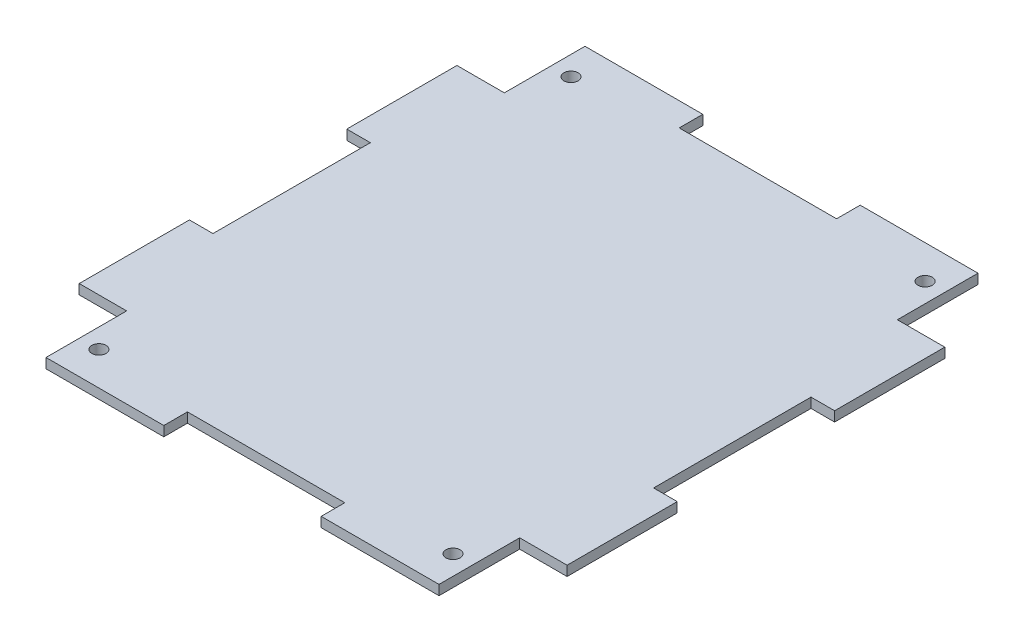
SolidWorks part; units mm, degrees
ref_plane "Front Plane" through (0, 0, 0) normal (0, 0, 1) x (1, 0, 0)
ref_plane "Top Plane" through (0, 0, 0) normal (0, 1, 0) x (1, 0, 0)
ref_plane "Right Plane" through (0, 0, 0) normal (1, 0, 0) x (0, 0, -1)
sketch "Sketch1" plane through (0, 0, 0) normal (0, 1, 0) x (1, 0, 0)
  line L0 (-25.4, 86.995) -> (-63.4314, 86.995)
  line L1 (-88.9, -101.6) -> (88.9, -101.6) construction
  line L2 (101.6, -88.9) -> (101.6, 88.9) construction
  line L3 (88.9, 101.6) -> (-88.9, 101.6) construction
  line L4 (-78.74, -60.96) -> (-63.4314, -60.96)
  line L5 (-63.4314, -60.96) -> (-63.4314, -86.995)
  line L6 (-63.4314, -86.995) -> (-25.4, -86.995)
  line L7 (63.4314, -86.995) -> (63.4314, -60.96)
  line L8 (63.4314, -60.96) -> (78.74, -60.96)
  line L9 (78.74, -60.96) -> (78.74, -25.4)
  line L10 (78.74, 60.96) -> (63.4314, 60.96)
  line L11 (63.4314, 60.96) -> (63.4314, 86.995)
  line L12 (63.4314, 86.995) -> (25.4, 86.995)
  line L13 (-63.4314, 86.995) -> (-63.4314, 60.96)
  line L14 (-63.4314, 60.96) -> (-78.74, 60.96)
  line L15 (-78.74, 60.96) -> (-78.74, 25.4)
  line L16 (-78.74, -25.4) -> (-78.74, -60.96)
  line L17 (-78.74, -25.4) -> (-71.12, -25.4)
  line L19 (-78.74, 25.4) -> (-71.12, 25.4)
  line L20 (-71.12, -25.4) -> (-71.12, 25.4)
  line L22 (-25.4, 86.995) -> (-25.4, 79.375)
  line L23 (-25.4, 79.375) -> (25.4, 79.375)
  line L24 (25.4, 86.995) -> (25.4, 79.375)
  line L25 (78.74, 25.4) -> (71.12, 25.4)
  line L27 (78.74, -25.4) -> (71.12, -25.4)
  line L28 (71.12, 25.4) -> (71.12, -25.4)
  line L30 (25.4, -86.995) -> (25.4, -79.375)
  line L31 (25.4, -79.375) -> (-25.4, -79.375)
  line L32 (-25.4, -86.995) -> (-25.4, -79.375)
  line L33 (78.74, 25.4) -> (78.74, 60.96)
  line L34 (25.4, -86.995) -> (63.4314, -86.995)
  line L35 (-101.6, 88.9) -> (-101.6, -88.9) construction
  arc A0 (88.9, -101.6) -> (101.6, -88.9) centre (88.9, -88.9) ccw construction
  arc A1 (-101.6, -88.9) -> (-88.9, -101.6) centre (-88.9, -88.9) ccw construction
  arc A2 (101.6, 88.9) -> (88.9, 101.6) centre (88.9, 88.9) ccw construction
  arc A3 (-101.6, 88.9) -> (-88.9, 101.6) centre (-88.9, 88.9) cw construction
  circle A4 centre (-57.15, 76.2) radius 2.286
  circle A5 centre (57.15, 76.2) radius 2.286
  circle A6 centre (57.15, -76.2) radius 2.286
  circle A7 centre (-57.15, -76.2) radius 2.286
  point P3 (0, 101.6)
  point P5 (101.6, 0)
  point P13 (101.6, 101.6)
  point P16 (-101.6, 101.6)
  point P38 (-71.12, 0)
  point P55 (0, -79.375)
  point P56 (0, 79.375)
  point P57 (71.12, 0)
  dimension "D2" = 12.7
  dimension "D11" = 4.572
  dimension "D8" = 44.45
  dimension "D1" = 203.2
  dimension "D3" = 203.2
  dimension "D4" = 22.86
  dimension "D5" = 15.3086
  dimension "D6" = 35.56
  dimension "D7" = 173.99
  dimension "D12" = 50.8
  dimension "D13" = 25.4
  dimension "D14" = 44.45
  dimension "D15" = 25.4
  dimension "D18" = 7.62
extrude "Boss-Extrude1" add sketch "Sketch1" along normal blind 3.175
